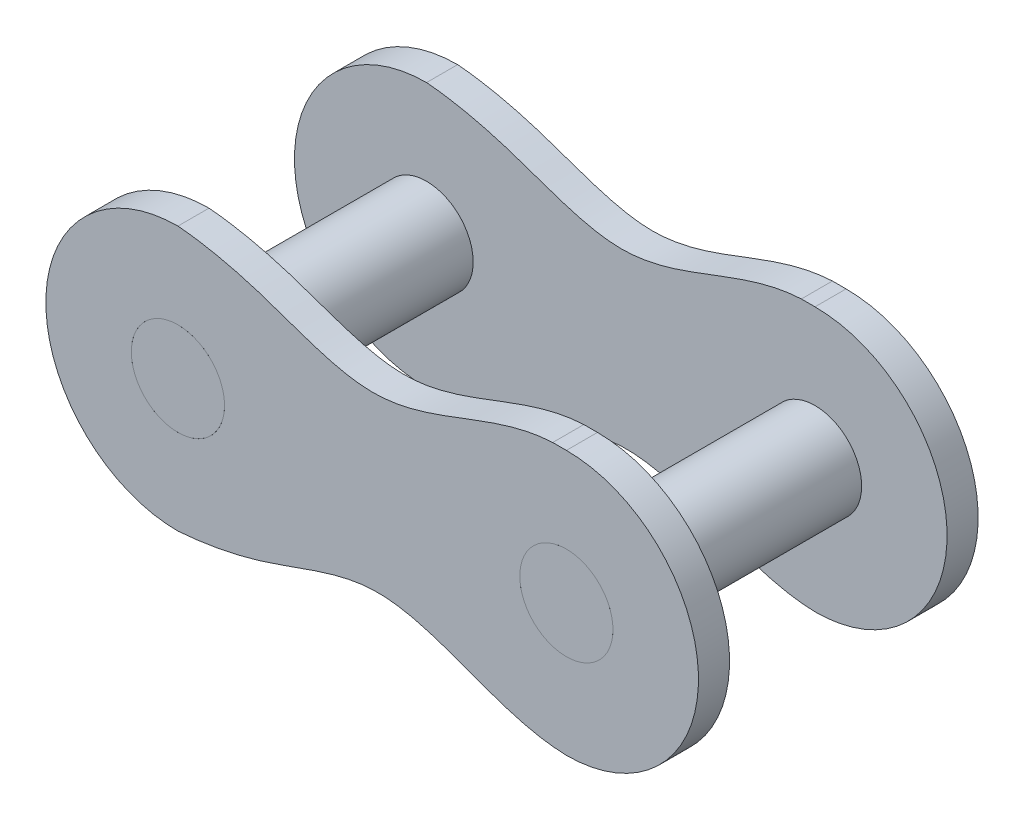
SolidWorks part; units mm, degrees
material "Alloy Steel"
ref_plane "Front Plane" through (0, 0, 0) normal (0, 0, 1) x (1, 0, 0)
ref_plane "Top Plane" through (0, 0, 0) normal (0, 1, 0) x (1, 0, 0)
ref_plane "Right Plane" through (0, 0, 0) normal (1, 0, 0) x (0, 0, -1)
sketch "Sketch2" plane through (0, 0, 0) normal (0, 0, 1) x (1, 0, 0)
  line L0 (-6.25, -4.25) -> (-11.0801, -4.25)
  line L3 (6.25, 4.25) -> (5.8107, 4.25)
  line L4 (-11.0801, -4.25) -> (-11.0801, 4.25)
  line L7 (-6.25, 4.25) -> (-11.0801, 4.25)
  circle A0 centre (-6.25, 0) radius 3.75
  circle A1 centre (6.25, 0) radius 3.75
  circle A2 centre (-6.25, 0) radius 1.5
  circle A3 centre (6.25, 0) radius 1.5
  arc A4 (-6.25, 4.25) -> (-5.1684, -4.1101) centre (-6.25, 0) ccw
  arc A5 (6.25, -4.25) -> (6.25, 4.25) centre (6.25, 0) ccw
  spline S0 degree 3 poles (6.25, 4.25) (4.0656, 4.362) (0.9195, 1.8098) (-3.2704, 3.7041) (-5.3938, 4.1795) (-6.25, 4.25) knots 0 0 0 0 0.337859 0.530611 0.675339 0.675339 0.675339 0.675339
  spline S1 degree 3 poles (6.25, -4.25) (3.9847, -4.1914) (0.9408, -1.7895) (-3.2736, -3.8097) (-5.3943, -4.1861) (-6.25, -4.25) knots 0 0 0 0 0.337859 0.530611 0.675339 0.675339 0.675339 0.675339
  point P7 (0, 0)
  dimension "D2" = 7.5
  dimension "D3" = 7.5
  dimension "D4" = 3
  dimension "D5" = 3
  dimension "D1" = 12.5
  dimension "D6" = 8.5
  dimension "D8" = 6.25
extrude "Boss-Extrude1" add sketch "Sketch2" along normal mid plane 1 contours S1 A5 L3 S0 A4 A1 A0 | A1 A3 | A0 A2 region at (-0.003, 0.0062, 0) region at (-9.8939, 0, 0) region at (2.6061, 0, 0)
sketch "Sketch5" plane through (0, 0, 0.5) normal (0, 0, 1) x (1, 0, 0)
  circle A0 centre (-6.25, 0) radius 1.5
  circle A1 centre (6.25, 0) radius 1.5
extrude "Boss-Extrude4" add sketch "Sketch5" along normal blind 7
ref_plane "Plane1" through (0, 0, 4) normal (0, 0, 1) x (1, 0, 0)
mirror "Mirror1" about plane through (0, 0, 4) normal (0, 0, 1) of bodies 101
loft "Loft1" add section face at (-4.75, 0, 7.5) section edge at (-4.75, 0, 8.5) connector at (-4.8393, -0.5099, 7.5) connector at (-4.7515, -0.0678, 8.5)
loft "Loft3" add section edge at (-4.75, 0, 0.5) section edge at (-4.75, 0, -0.5) connector at (-5.529, -1.3154, 0.5) connector at (-5.0636, -0.9179, -0.5)
loft "Loft4" add section edge at (7.75, 0, 0.5) section edge at (7.75, 0, -0.5) connector at (7.6889, -0.4239, 0.5) connector at (7.5011, -0.8275, -0.5)
loft "Loft5" add section edge at (7.75, 0, 7.5) section edge at (7.75, 0, 8.5) connector at (6.3414, -1.4972, 7.5) connector at (5.6586, -1.3785, 8.5)
ref_plane "Plane2" through (0, 0, 4) normal (0, 0, 1) x (1, 0, 0)
